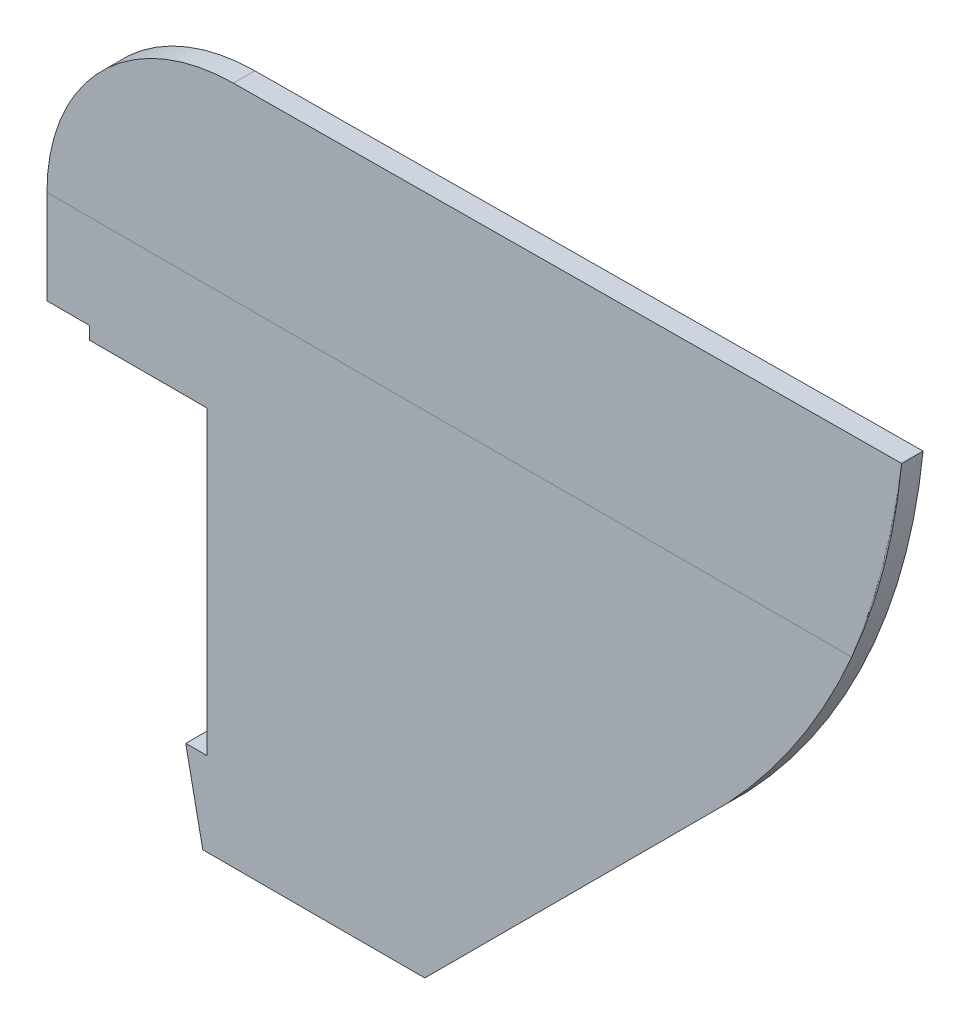
SolidWorks part; units mm, degrees
ref_plane "Plan de face" through (0, 0, 0) normal (0, 0, 1) x (1, 0, 0)
ref_plane "Plan de dessus" through (0, 0, 0) normal (0, 1, 0) x (1, 0, 0)
ref_plane "Plan de droite" through (0, 0, 0) normal (1, 0, 0) x (0, 0, -1)
sketch "Esquisse1" plane through (0, 0, 0) normal (0, 0, 1) x (1, 0, 0)
  line L0 (0, 0) -> (188.5, 0) construction
  line L1 (0, 0) -> (0, -25)
  line L2 (0, -25) -> (37.5, -25)
  line L3 (37.5, -25) -> (37.5, -95.5)
  line L4 (37.5, -95.5) -> (32.5, -95.5)
  line L5 (32.5, -95.5) -> (36.4874, -115.0985)
  line L6 (36.4874, -115.0985) -> (88.4874, -115.0985)
  line L7 (88.4874, -115.0985) -> (159.198, -44.3878)
  line L8 (43.6829, 43.9989) -> (200.1829, 45.1267)
  arc A0 (0, 0) -> (43.6829, 43.9989) centre (44, 0) cw
  arc A1 (159.198, -44.3878) -> (200.1829, 45.1267) centre (49.0805, 60.1702) ccw
  dimension "D11" = 44
  dimension "D1" = 188.5
  dimension "D2" = 25
  dimension "D3" = 37.5
  dimension "D4" = 90
  dimension "D5" = 70.5
  dimension "D6" = 5
  dimension "D7" = 20
  dimension "D8" = 52
  dimension "D9" = 135
  dimension "D10" = 100
  dimension "D12" = 156.5
extrude "Boss.-Extru.1" add sketch "Esquisse1" along normal blind 5
sketch "Esquisse2" plane through (0, 0, 5) normal (0, 0, 1) x (1, 0, 0)
  line L0 (0, 0) -> (188.5, 0)
  line L1 (200.1829, 45.1267) -> (43.6829, 43.9989)
  arc A0 (188.5, 0) -> (200.1829, 45.1267) centre (16.1609, 68.6928) ccw
  arc A1 (43.6829, 43.9989) -> (0, 0) centre (44, 0) ccw
  dimension "D1" = 188.5
extrude "Boss.-Extru.2" add sketch "Esquisse2" along normal blind 0.01
sketch "Esquisse3" plane through (0, 0, 5) normal (0, 0, 1) x (1, 0, 0)
  line L1 (0, -25) -> (10, -25)
  line L2 (0, -25) -> (0, -22)
  line L3 (0, -22) -> (10, -22)
  line L4 (10, -25) -> (10, -22)
  dimension "D1" = 10
  dimension "D2" = 3
extrude "Enlèv. mat.-Extru.1" cut sketch "Esquisse3" against normal through all
